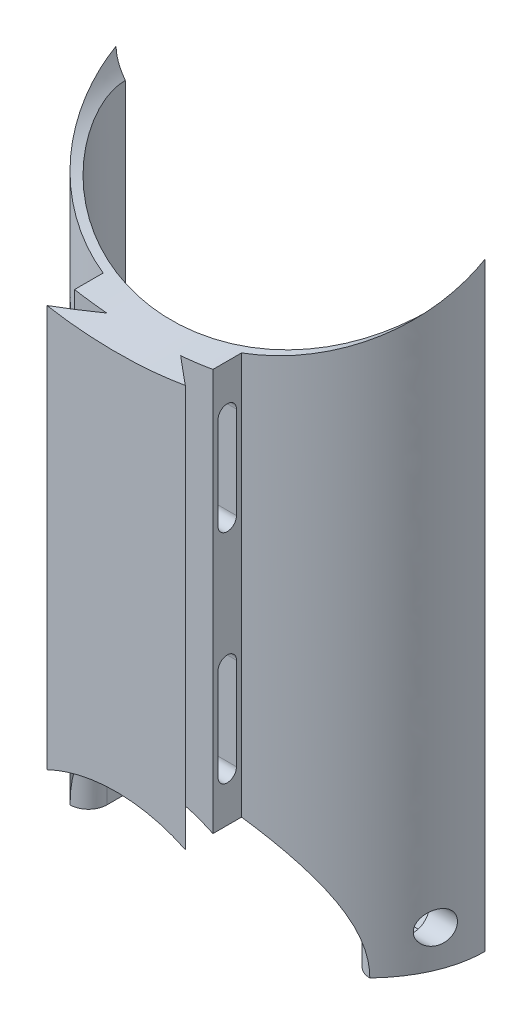
SolidWorks part; units mm, degrees
material "PLA"
ref_plane "Front Plane" through (0, 0, 0) normal (0, 0, 1) x (1, 0, 0)
ref_plane "Top Plane" through (0, 0, 0) normal (0, 1, 0) x (1, 0, 0)
ref_plane "Right Plane" through (0, 0, 0) normal (1, 0, 0) x (0, 0, -1)
sketch "Sketch1" plane through (0, 0, 0) normal (0, 1, 0) x (1, 0, 0)
  ellipse E0 centre (0, 0) end of major axis (25.4, 0) minor radius 19.05
  dimension "D1" = 50.8
  dimension "D2" = 38.1
extrude "Boss-Extrude1" add sketch "Sketch1" along normal blind 82.55 contours E0
shell "Shell1" thickness 1.27 removed face at (25.4, 82.55, 0) removed face at (25.4, 0, 0)
sketch "Sketch3" plane through (0, 0, 0) normal (0, 0, 1) x (1, 0, 0)
  line L1 (29.1836, -15.0653) -> (-40.8926, -15.0653)
  line L2 (29.1836, -15.0653) -> (29.1836, 110.7022)
  line L3 (29.1836, 110.7022) -> (-40.8926, 110.7022)
  line L4 (-40.8926, -15.0653) -> (-40.8926, 110.7022)
extrude "Cut-Extrude1" cut sketch "Sketch3" against normal up to surface up to face at (25.4, 82.55, 0)
ref_plane "Plane4" through (0, 0, 19.05) normal (0, 0, 1) x (1, 0, 0)
sketch "Sketch4" plane through (0, 0, 19.05) normal (0, 0, 1) x (1, 0, 0)
  line L1 (9.525, 82.55) -> (-9.525, 82.55)
  line L2 (9.525, 82.55) -> (9.525, 0)
  line L3 (9.525, 0) -> (-9.525, 0)
  line L4 (-9.525, 82.55) -> (-9.525, 0)
  line L6 (25.4, 82.55) -> (25.4, 0) construction
  line L7 (-25.4, 0) -> (25.4, 0) construction
  line L8 (25.4, 82.55) -> (-25.4, 82.55) construction
  dimension "D1" = 19.05
  dimension "D4" = 15.875
extrude "Boss-Extrude2" add sketch "Sketch4" against normal up to surface up to face at (0, 41.275, 9.525)
sketch "Sketch6" plane through (0, 0, 19.05) normal (0, 0, 1) x (1, 0, 0)
  line L4 (-9.525, 0) -> (9.525, 0)
  line L5 (9.525, 0) -> (9.525, 82.55)
  line L6 (9.525, 82.55) -> (-9.525, 82.55)
  line L7 (-9.525, 82.55) -> (-9.525, 0)
  line L8 (-9.525, 0) -> (9.525, 0)
  line L9 (9.525, 0) -> (9.525, 82.55)
  line L10 (9.525, 82.55) -> (-9.525, 82.55)
  line L11 (-9.525, 82.55) -> (-9.525, 0)
  dimension "D1" = 0
extrude "Boss-Extrude4" add sketch "Sketch6" along normal blind 6.35
sketch "Sketch7" plane through (0, 0, 0) normal (0, -1, 0) x (1, 0, 0)
  line L0 (-9.525, 25.4) -> (-5.08, 21.59)
  line L1 (9.525, 25.4) -> (5.08, 21.59)
  line L2 (-5.08, 21.59) -> (-9.525, 21.59)
  line L3 (-9.525, 17.6598) -> (-9.525, 25.4) construction
  line L4 (-9.525, 21.59) -> (-9.525, 25.4)
  line L5 (5.08, 21.59) -> (9.525, 21.59)
  line L6 (9.525, 17.6598) -> (9.525, 25.4) construction
  line L7 (9.525, 21.59) -> (9.525, 25.4)
  line L8 (-9.525, 25.4) -> (9.525, 25.4) construction
  dimension "D2" = 3.81
  dimension "D3" = 10.16
extrude "Cut-Extrude2" cut sketch "Sketch7" against normal through all
sketch "Sketch8" plane through (0, 0, 19.05) normal (0, 0, 1) x (1, 0, 0)
  line L0 (9.525, 82.55) -> (-9.525, 82.55) construction
  line L1 (-9.525, 82.55) -> (-25.4, 82.55) construction
  ellipse E0 centre (0, 0) end of major axis (-20.6375, 0) minor radius 19.05
  ellipse E1 centre (0, 82.55) end of major axis (25.4, 82.55) minor radius 11.1125
  dimension "D1" = 38.1
  dimension "D2" = 41.275
  dimension "D3" = 22.225
extrude "Cut-Extrude3" cut sketch "Sketch8" against normal through all both and the other way through all
sketch "Sketch10" plane through (9.525, 0, 0) normal (1, 0, 0) x (0, 0, -1)
  line L0 (-19.6215, 23.2496) -> (-19.6215, 35.9496) construction
  line L2 (-20.8915, 23.2496) -> (-20.8915, 35.9496)
  line L3 (-18.3515, 23.2496) -> (-18.3515, 35.9496)
  line L4 (-17.6598, 16.8996) -> (-21.59, 16.8996) construction
  line L6 (-21.59, 72.2484) -> (-21.59, 16.8996) construction
  line L7 (-19.6215, 53.1984) -> (-19.6215, 65.8984) construction
  line L8 (-20.8915, 53.1984) -> (-20.8915, 65.8984)
  line L9 (-18.3515, 53.1984) -> (-18.3515, 65.8984)
  line L10 (-21.59, 72.2484) -> (-17.6598, 72.2484) construction
  arc A0 (-20.8915, 23.2496) -> (-18.3515, 23.2496) centre (-19.6215, 23.2496) ccw
  arc A1 (-18.3515, 35.9496) -> (-20.8915, 35.9496) centre (-19.6215, 35.9496) ccw
  arc A2 (-20.8915, 53.1984) -> (-18.3515, 53.1984) centre (-19.6215, 53.1984) ccw
  arc A3 (-18.3515, 65.8984) -> (-20.8915, 65.8984) centre (-19.6215, 65.8984) ccw
  point P4 (-19.6215, 29.5996)
  point P13 (-19.6215, 59.5484)
  dimension "D3" = 1.27
  dimension "D6" = 1.27
  dimension "D1" = 12.7
  dimension "D2" = 12.7
  dimension "D4" = 1.9685
  dimension "D5" = 12.7
  dimension "D7" = 12.7
extrude "Cut-Extrude4" cut sketch "Sketch10" against normal through all
ref_plane "Plane7" through (20.6375, 0, 0) normal (1, 0, 0) x (0, 0, -1)
ref_plane "Plane8" through (18.0975, 0, 0) normal (1, 0, 0) x (0, 0, -1)
sketch "Sketch14" plane through (18.0975, 0, 0) normal (1, 0, 0) x (0, 0, -1)
  line L1 (-11.1054, 0) -> (0, 0)
  line L2 (-11.1054, 0) -> (-11.1054, 10.16)
  line L3 (-11.1054, 10.16) -> (0, 10.16)
  line L4 (0, 0) -> (0, 10.16)
  dimension "D1" = 10.16
extrude "Boss-Extrude7" add sketch "Sketch14" along normal up to body separate body
sketch "Sketch15" plane through (18.0975, 0, 0) normal (-1, 0, 0) x (0, 0, 1)
  line L2 (11.1054, 10.16) -> (11.1054, 0) construction
  line L3 (11.1054, 0) -> (0, 0) construction
  circle A0 centre (5.5555, 5.08) radius 2.159
  dimension "D1" = 4.318
  dimension "D2" = 5.5499
  dimension "D3" = 5.08
extrude "Cut-Extrude7" cut sketch "Sketch15" against normal through all
sketch "Sketch16" plane through (18.0975, 0, 0) normal (-1, 0, 0) x (0, 0, 1)
  line L0 (0, 10.16) -> (11.1054, 10.16) construction
  line L1 (7.5719, 1.5875) -> (9.5883, 5.08)
  line L2 (9.5883, 5.08) -> (7.5719, 8.5725)
  line L3 (7.5719, 8.5725) -> (3.5391, 8.5725)
  line L4 (3.5391, 8.5725) -> (1.5227, 5.08)
  line L5 (1.5227, 5.08) -> (3.5391, 1.5875)
  line L6 (3.5391, 1.5875) -> (7.5719, 1.5875)
  circle A0 centre (5.5555, 5.08) radius 3.4925 construction
  dimension "D1" = 6.985
extrude "Cut-Extrude8" cut sketch "Sketch16" against normal blind 3.048
mirror "Mirror5" about plane through (0, 0, 0) normal (1, 0, 0) of "Cut-Extrude7", "Boss-Extrude7", "Cut-Extrude8"
fillet "Fillet2" radius 2.54 2 edges at (18.0975, 5.08, 11.1054) (-18.0975, 5.08, 11.1054)
